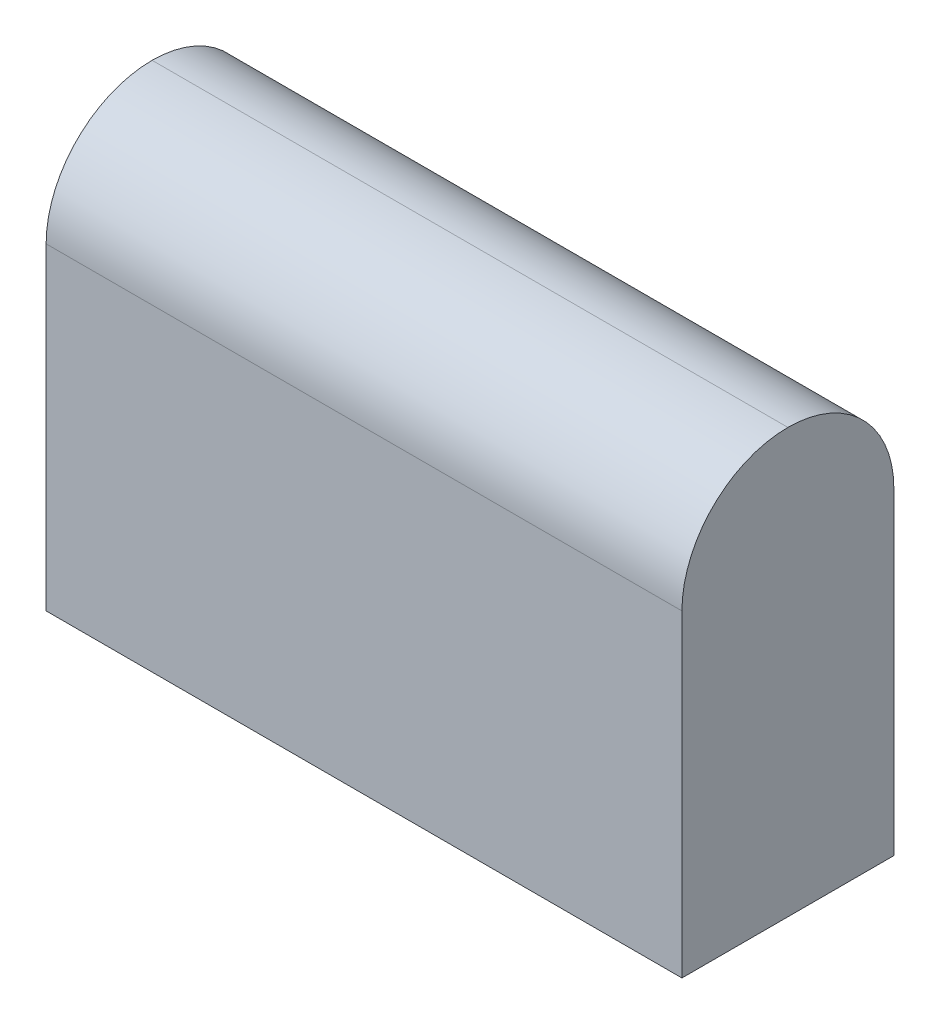
SolidWorks part; units mm, degrees
ref_plane "Front Plane" through (0, 0, 0) normal (0, 0, 1) x (1, 0, 0)
ref_plane "Top Plane" through (0, 0, 0) normal (0, 1, 0) x (1, 0, 0)
ref_plane "Right Plane" through (0, 0, 0) normal (1, 0, 0) x (0, 0, -1)
sketch "Sketch1" plane through (0, 0, 0) normal (0, 1, 0) x (1, 0, 0)
  line L1 (1.5, -0.5) -> (-1.5, -0.5)
  line L2 (1.5, -0.5) -> (1.5, 0.5)
  line L3 (1.5, 0.5) -> (-1.5, 0.5)
  line L4 (-1.5, -0.5) -> (-1.5, 0.5)
  line L5 (1.5, -0.5) -> (-1.5, 0.5) construction
  line L6 (1.5, 0.5) -> (-1.5, -0.5) construction
  point P0 (0, 0)
  dimension "D1" = 3
  dimension "D2" = 1
extrude "Boss-Extrude1" add sketch "Sketch1" along normal blind 2
fillet "Fillet1" radius 0.5 2 edges at (0, 2, -0.5) (0, 2, 0.5)
